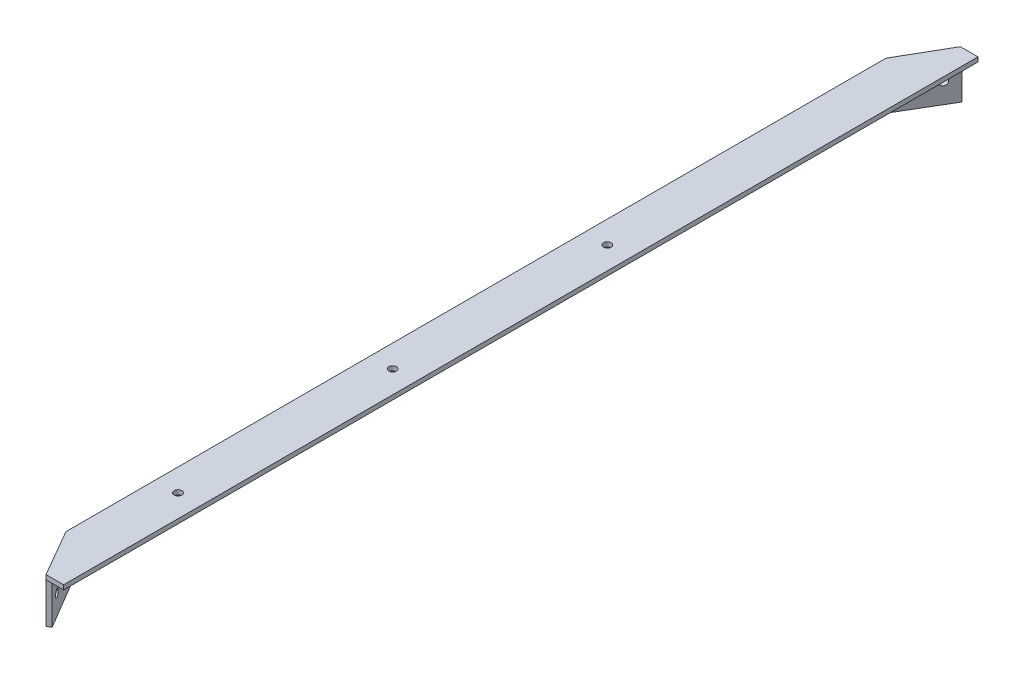
SolidWorks part; units mm, degrees
material "1.0116 (S235J2G3)"
ref_plane "Front Plane" through (0, 0, 0) normal (0, 0, 1) x (1, 0, 0)
ref_plane "Top Plane" through (0, 0, 0) normal (0, 1, 0) x (1, 0, 0)
ref_plane "Right Plane" through (0, 0, 0) normal (1, 0, 0) x (0, 0, -1)
sketch "Sketch1" plane through (0, 0, 0) normal (0, 0, 1) x (1, 0, 0)
  line L6 (0, 0) -> (0, 70)
  line L7 (0, 70) -> (70, 70)
  line L8 (70, 70) -> (70, 63)
  line L9 (70, 63) -> (7, 63)
  line L10 (7, 63) -> (7, 0)
  line L11 (7, 0) -> (0, 0)
  dimension "D1" = 70
  dimension "D2" = 70
  dimension "D3" = 7
  dimension "D4" = 7
extrude "Boss-Extrude1" add sketch "Sketch1" along normal blind 640
sketch "Sketch21" plane through (0, 0, 0) normal (0, 0, -1) x (-1, 0, 0)
  line L0 (0, 70) -> (-70, 70) construction
  line L1 (-70, 70) -> (-70, 0) construction
  line L2 (-70, 0) -> (0, 0) construction
  line L3 (0, 0) -> (0, 69.2595) construction
sketch "Sketch23" plane through (0, 0, 0) normal (0, 1, 0) x (1, 0, 0)
  line L0 (0, -640) -> (42.5, -713.6122)
  line L1 (42.5, -713.6122) -> (48.5622, -710.1122)
  line L2 (48.5622, -710.1122) -> (7, -640)
  line L3 (7, -640) -> (0, -640)
  line L4 (0, -38.5) -> (0, 38.5) construction
  dimension "D1" = 7
  dimension "D2" = 210
  dimension "D3" = 85
extrude "Boss-Extrude2" add sketch "Sketch23" along normal blind 63
sketch "Sketch25" plane through (0, 63, 0) normal (0, 1, 0) x (1, 0, 0)
  line L0 (70, -640) -> (0, -640)
  line L1 (70, -640) -> (70, 0) construction
  line L2 (7, -640) -> (70, -640) construction
  line L3 (0, -640) -> (42.5, -713.6122) construction
  line L4 (0, -640) -> (42.5, -713.6122)
  line L5 (42.5, -713.6122) -> (48.5622, -710.1122) construction
  line L6 (42.5, -713.6122) -> (70, -713.6122)
  line L7 (70, -713.6122) -> (70, -640)
extrude "Boss-Extrude3" add sketch "Sketch25" along normal blind 7
sketch "Sketch26" plane through (-275.5567, 0, 163.3488) normal (0.8602, 0, -0.5099) x (-0.5099, 0, -0.8602)
  line L0 (-635.6125, 0) -> (-554.1071, 0) construction
  line L1 (-635.6125, 63) -> (-635.6125, 0) construction
  line L2 (-554.1071, 0) -> (-554.1071, 63) construction
  circle A0 centre (-614.3625, 31.5) radius 6
  circle A1 centre (-575.3571, 31.5) radius 6
  dimension "D1" = 12
  dimension "D2" = 12
  dimension "D3" = 31.5
  dimension "D4" = 31.5
  dimension "D5" = 21.25
  dimension "D6" = 21.25
extrude "Cut-Extrude2" cut sketch "Sketch26" against normal blind 10
mirror "Mirror1" about plane through (0, 0, 0) normal (0, 0, 1) of bodies 119 116
sketch "Sketch28" plane through (0, 70, 0) normal (0, 1, 0) x (1, 0, 0)
  line L0 (70, -713.6122) -> (70, 713.6122) construction
  circle A0 centre (35, -500) radius 6
  circle A1 centre (35, -165) radius 6
  circle A2 centre (35, 170) radius 6
  dimension "D1" = 12
  dimension "D2" = 12
  dimension "D3" = 12
  dimension "D4" = 335
  dimension "D5" = 335
  dimension "D6" = 500
  dimension "D7" = 35
  dimension "D8" = 35
  dimension "D9" = 35
extrude "Cut-Extrude1" cut sketch "Sketch28" against normal blind 10 and the other way blind 10
